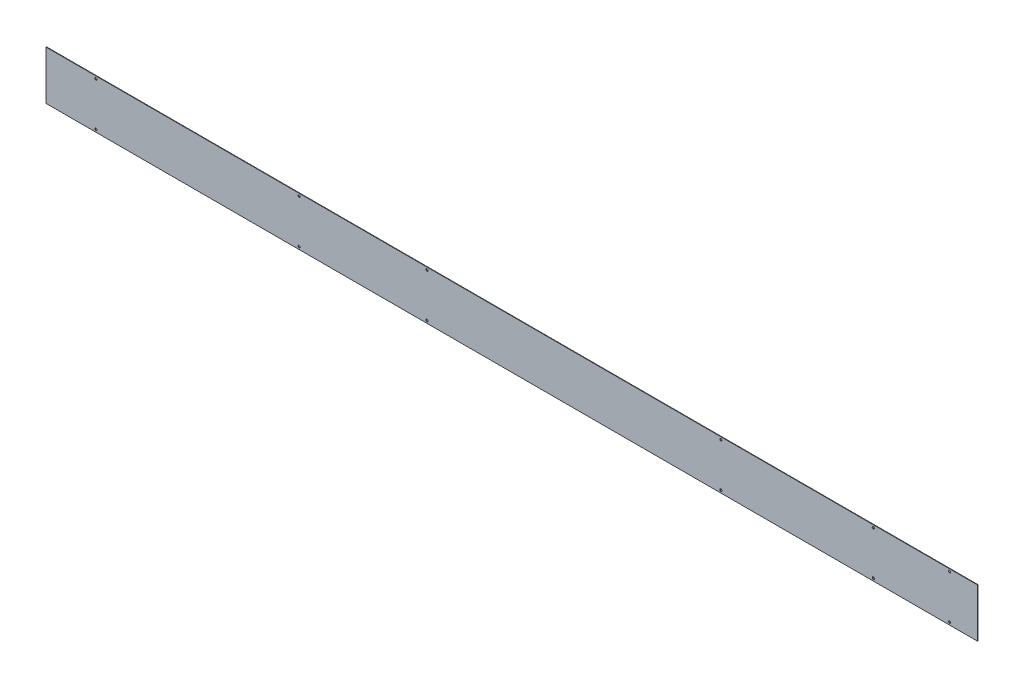
SolidWorks part; units mm, degrees
ref_plane "Front Plane" through (0, 0, 0) normal (0, 0, 1) x (1, 0, 0)
ref_plane "Top Plane" through (0, 0, 0) normal (0, 1, 0) x (1, 0, 0)
ref_plane "Right Plane" through (0, 0, 0) normal (1, 0, 0) x (0, 0, -1)
sketch "Sketch2" plane through (0, 0, 0) normal (0, 0, 1) x (1, 0, 0)
  line L1 (-698.5, -36.576) -> (698.5, -36.576)
  line L2 (-698.5, -36.576) -> (-698.5, 36.576)
  line L3 (-698.5, 36.576) -> (698.5, 36.576)
  line L4 (698.5, -36.576) -> (698.5, 36.576)
  line L5 (-698.5, -36.576) -> (698.5, 36.576) construction
  line L6 (-698.5, 36.576) -> (698.5, -36.576) construction
  point P0 (0, 0)
  dimension "D1" = 1397
  dimension "D2" = 73.152
base flange "Base-Flange1" sketch "Sketch2" thickness 0.7595 reverse thickness direction no parameters "D1"=0.7366
sketch "Sketch3" plane through (0, 0, 0) normal (0, 0, 1) x (1, 0, 0)
  line L0 (698.5, 36.576) -> (-698.5, 36.576) construction
  line L1 (-698.5, -36.576) -> (698.5, -36.576) construction
  line L2 (-698.5, 36.576) -> (-698.5, -36.576) construction
  circle A0 centre (-623.57, 32.766) radius 1.651
  circle A1 centre (-623.57, -32.766) radius 1.651
  circle A2 centre (-127, 32.766) radius 1.651
  circle A3 centre (-127, -32.766) radius 1.651
  circle A4 centre (313.69, 32.766) radius 1.651
  circle A5 centre (313.69, -32.766) radius 1.651
  circle A6 centre (542.29, 32.766) radius 1.651
  circle A7 centre (542.29, -32.766) radius 1.651
  circle A8 centre (656.59, 32.766) radius 1.651
  circle A9 centre (656.59, -32.766) radius 1.651
  circle A10 centre (-318.77, 32.766) radius 1.651
  circle A11 centre (-318.77, -32.766) radius 1.651
  dimension "D1" = 3.302
  dimension "D2" = 3.81
  dimension "D3" = 3.81
  dimension "D4" = 74.93
  dimension "D5" = 496.57
  dimension "D6" = 440.69
  dimension "D7" = 228.6
  dimension "D8" = 114.3
  dimension "D9" = 304.8
extrude "Cut-Extrude1" cut sketch "Sketch3" against normal through all both and the other way through all normal cut yes
sketch "Bend-Lines1" [suppressed] plane through (0, 0, 0) normal (0, 1, 0) x (1, 0, 0)
sketch "Bounding-Box1" [suppressed] plane through (0, 0, 0) normal (0, 1, 0) x (1, 0, 0)
sheet metal parameters "Sheet-Metal1" thickness 0.7595 parameters "D1"=0.7366
flat pattern "Flat-Pattern1" [suppressed]
sketch "Bend-Lines2" plane through (0, 0, 0) normal (0, 1, 0) x (1, 0, 0)
sketch3d "Bounding-Box2" [suppressed]
  line L0 (-698.5, -36.576, 0) -> (698.5, -36.576, 0) construction
  line L1 (-698.5, 36.576, 0) -> (698.5, 36.576, 0) construction
  line L2 (-698.5, -36.576, 0) -> (-698.5, 36.576, 0) construction
  line L3 (698.5, -36.576, 0) -> (698.5, 36.576, 0) construction
sheet metal parameters "Sheet-Metal4" thickness 0.7595 parameters "D1"=0.7366
flat pattern "Flat-Pattern1"
sketch "Bend-Lines2" plane through (0, 0, 0) normal (0, 1, 0) x (1, 0, 0)
sketch3d "Bounding-Box2" [suppressed]
  line L0 (-698.5, -36.576, 0) -> (698.5, -36.576, 0) construction
  line L1 (-698.5, 36.576, 0) -> (698.5, 36.576, 0) construction
  line L2 (-698.5, -36.576, 0) -> (-698.5, 36.576, 0) construction
  line L3 (698.5, -36.576, 0) -> (698.5, 36.576, 0) construction
